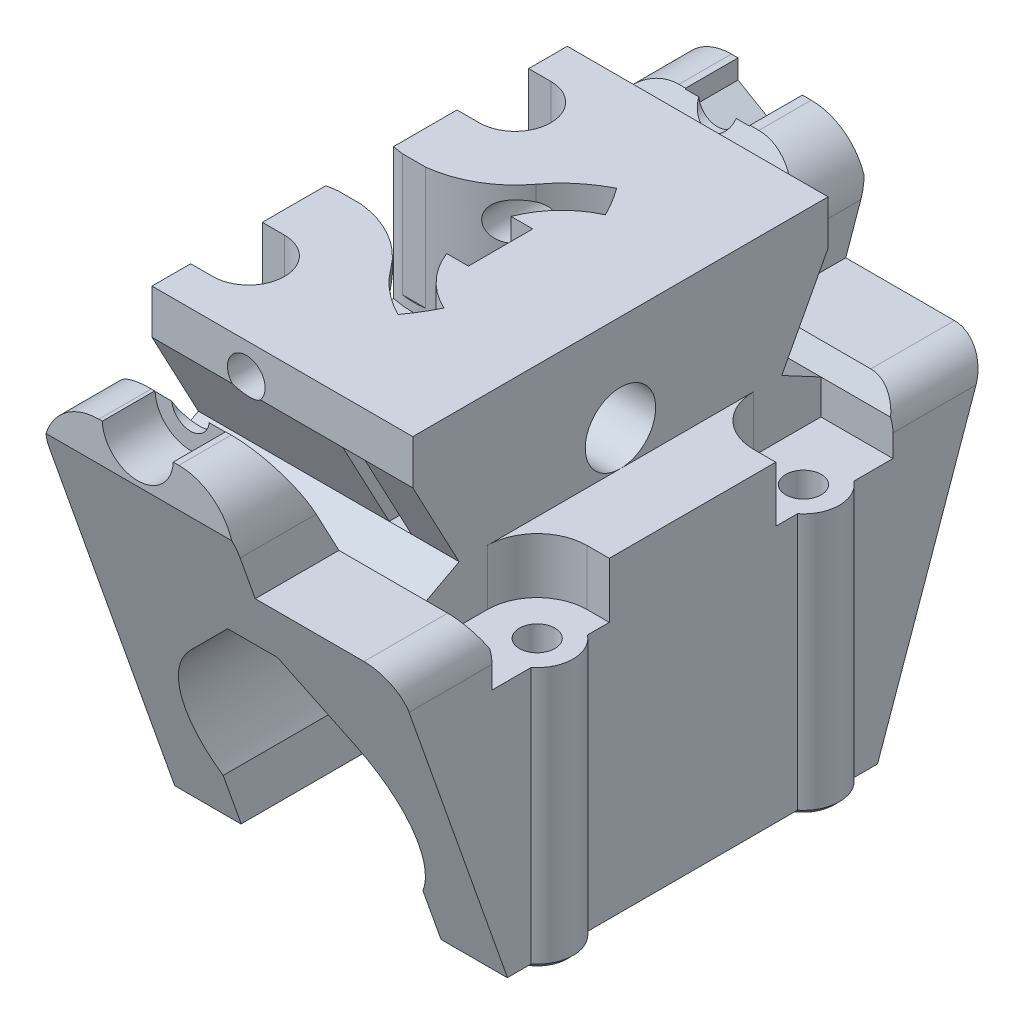
SolidWorks part; units mm, degrees
ref_plane "Front Plane" through (0, 0, 0) normal (0, 0, 1) x (1, 0, 0)
ref_plane "Top Plane" through (0, 0, 0) normal (0, 1, 0) x (1, 0, 0)
ref_plane "Right Plane" through (0, 0, 0) normal (1, 0, 0) x (0, 0, -1)
sketch "Sketch2" plane through (0, 0, 0) normal (1, 0, 0) x (0, 0, -1)
  line L0 (-104.5, 178.7) -> (-15, 10.5) construction
  line L1 (-15, -10.5) -> (15, -10.5) construction
  line L2 (-15, -10.5) -> (-15, 10.5) construction
  line L3 (-15, 10.5) -> (15, 10.5) construction
  line L4 (15, -10.5) -> (15, 10.5) construction
  line L5 (-15, -10.5) -> (15, 10.5) construction
  line L6 (-15, 10.5) -> (15, -10.5) construction
  line L7 (-18.7166, 26) -> (18.7166, 26) construction
  line L8 (0, 26) -> (0, -12.5) construction
  line L9 (-28.5, -10.5) -> (28.5, -10.5)
  line L10 (14.536, 18.1432) -> (18.7166, 26)
  line L11 (-16, 26) -> (28.5, -10.5) construction
  line L12 (-28.5, -10.5) -> (16, 26) construction
  line L13 (-29.5081, -14.5) -> (29.5081, -14.5) construction
  line L14 (-29.5081, -14.5) -> (-29.5081, -10.5) construction
  line L15 (-29.5081, -10.5) -> (29.5081, -10.5) construction
  line L16 (29.5081, -14.5) -> (29.5081, -10.5) construction
  line L17 (-29.5081, -14.5) -> (29.5081, -10.5) construction
  line L18 (-29.5081, -10.5) -> (29.5081, -14.5) construction
  line L19 (-104.5, 178.7) -> (104.5, 178.7) construction
  line L20 (-104.5, 178.7) -> (-104.5, -30.3) construction
  line L21 (-104.5, -30.3) -> (104.5, -30.3) construction
  line L22 (104.5, 178.7) -> (104.5, -30.3) construction
  line L23 (-104.5, 178.7) -> (104.5, -30.3) construction
  line L24 (-104.5, -30.3) -> (104.5, 178.7) construction
  line L25 (-14.536, 18.1432) -> (-18.0672, 16.2643)
  line L26 (-14.536, 18.1432) -> (-18.7166, 26)
  line L27 (-18.0672, 16.2643) -> (-23.7797, 27)
  line L28 (-28.5, 27) -> (-28.5, -10.5)
  line L29 (14.536, 18.1432) -> (18.0672, 16.2643)
  line L30 (-18.7166, 26) -> (-22.2478, 24.121) construction
  line L31 (28.5, 27) -> (28.5, -10.5)
  line L32 (18.7166, 26) -> (18.7166, 30)
  line L33 (18.7166, 30) -> (-18.7166, 30)
  line L34 (-18.7166, 30) -> (-18.7166, 26)
  line L35 (18.0672, 16.2643) -> (23.7797, 27)
  line L36 (22.2478, 24.121) -> (28.5, 24.121) construction
  line L37 (18.7166, 26) -> (22.2478, 24.121) construction
  line L38 (-22.2478, 24.121) -> (-28.5, 24.121) construction
  line L39 (23.7797, 27) -> (28.5, 27)
  line L40 (-23.7797, 27) -> (-28.5, 27)
  point P0 (0, 0)
  point P6 (0, 12.8764)
  point P11 (0, -12.5)
  point P16 (0, 74.2)
  point P32 (0, -10.5)
  dimension "D1" = 21
  dimension "D2" = 30
  dimension "D3" = 32
  dimension "D4" = 26
  dimension "D5" = 4
  dimension "D6" = 17.8
  dimension "D7" = 209
  dimension "D8" = 184
  dimension "D9" = 57
  dimension "D10" = 4
  dimension "D11" = 4
  dimension "D12" = 3
extrude "Boss-Extrude1" add sketch "Sketch2" along normal blind 30
chamfer "Chamfer4" distance 34 distance2 12 1 edges at (15, -10.5, 28.5) first distance on face at (15, 8.25, 28.5)
chamfer "Chamfer3" distance 12 distance2 34 1 edges at (15, -10.5, -28.5) first distance on face at (15, -10.5, -6)
sketch "Sketch3" plane through (0, 0, -28.5) normal (0, 0, -1) x (-1, 0, 0)
  line L0 (-30, -10.5) -> (0, -10.5) construction
  line L1 (-24, -5.4083) -> (-24, -10.5)
  line L2 (-24, -10.5) -> (-6, -10.5)
  line L3 (-6, -10.5) -> (-6, -5.4083)
  line L4 (-15, 0) -> (-7.5754, 7.4246) construction
  line L5 (-7.5754, 7.4246) -> (-12.7508, 12.6)
  line L6 (-12.7508, 12.6) -> (-17.2492, 12.6)
  line L7 (-17.2492, 12.6) -> (-22.4246, 7.4246)
  line L8 (-22.4246, 7.4246) -> (-15, 0) construction
  arc A0 (-6, -5.4083) -> (-7.5754, 7.4246) centre (-15, 0) ccw
  arc A1 (-22.4246, 7.4246) -> (-24, -5.4083) centre (-15, 0) ccw
  point P2 (-15, -10.5)
  point P12 (-15, 10.5)
  dimension "D1" = 21
  dimension "D2" = 18
  dimension "D3" = 2.1
extrude "Cut-Extrude1" cut sketch "Sketch3" against normal through all
sketch "Sketch4" plane through (0, -10.5, 0) normal (0, -1, 0) x (1, 0, 0)
  line L0 (0, 0) -> (30, 0) construction
  line L1 (30, 16.5) -> (30, -16.5) construction
  line L3 (2, -12) -> (28, -12) construction
  line L4 (2, -12) -> (2, 12) construction
  line L5 (2, 12) -> (28, 12) construction
  line L6 (28, -12) -> (28, 12) construction
  line L7 (2, -12) -> (28, 12) construction
  line L8 (2, 12) -> (28, -12) construction
  circle A0 centre (28, 12) radius 1.6
  circle A1 centre (28, -12) radius 1.6
  circle A2 centre (2, -12) radius 1.6
  circle A3 centre (2, 12) radius 1.6
  point P5 (15, 0)
  dimension "D3" = 3.2
  dimension "D1" = 26
  dimension "D2" = 24
extrude "Cut-Extrude2" cut sketch "Sketch4" against normal through all
chamfer "Chamfer1" [suppressed] distance 11 distance2 8
sketch "Sketch5" plane through (0, -10.5, 0) normal (0, -1, 0) x (1, 0, 0)
  line L0 (30, 14.536) -> (30, 9.464)
  line L1 (30, 16.5) -> (30, -16.5) construction
  line L2 (0, 14.536) -> (0, 9.464)
  line L3 (0, -9.464) -> (0, -14.536)
  line L4 (30, -9.464) -> (30, -14.536)
  line L5 (0, 16.5) -> (0, -16.5) construction
  arc A0 (30, 9.464) -> (30, 14.536) centre (28, 12) ccw
  arc A1 (30, -14.536) -> (30, -9.464) centre (28, -12) ccw
  arc A2 (0, -9.464) -> (0, -14.536) centre (2, -12) ccw
  arc A3 (0, 14.536) -> (0, 9.464) centre (2, 12) ccw
  circle A5 centre (28, -12) radius 1.6 construction
extrude "Boss-Extrude2" add sketch "Sketch5" along direction (0, 1, 0) on the side against the normal through all
sketch "Sketch7" plane through (0, 30, 0) normal (0, 1, 0) x (1, 0, 0)
  line L0 (2, 8.7703) -> (-1.2297, 8.7703)
  line L1 (15, 19.7808) -> (15, -19.7808) construction
  line L4 (-1.2297, 8.7703) -> (-1.2297, 15.2297)
  line L5 (0, 0) -> (30, 0) construction
  line L6 (31.2297, 15.2297) -> (28, 15.2297)
  line L7 (-1.2297, 15.2297) -> (2, 15.2297)
  line L8 (31.2297, 8.7703) -> (31.2297, 15.2297)
  line L9 (28, 8.7703) -> (31.2297, 8.7703)
  line L10 (28, -8.7703) -> (31.2297, -8.7703)
  line L11 (31.2297, -8.7703) -> (31.2297, -15.2297)
  line L12 (-1.2297, -15.2297) -> (2, -15.2297)
  line L13 (31.2297, -15.2297) -> (28, -15.2297)
  line L14 (-1.2297, -8.7703) -> (-1.2297, -15.2297)
  line L15 (2, -8.7703) -> (-1.2297, -8.7703)
  arc A0 (2, 8.7703) -> (2, 15.2297) centre (2, 12) ccw
  arc A1 (28, 8.7703) -> (28, 15.2297) centre (28, 12) cw
  arc A2 (28, -8.7703) -> (28, -15.2297) centre (28, -12) ccw
  arc A3 (2, -8.7703) -> (2, -15.2297) centre (2, -12) cw
  arc A4 (0, 14.536) -> (0, 9.464) centre (2, 12) ccw construction
extrude "Cut-Extrude6" cut sketch "Sketch7" against normal offset from surface (7 mm away) 33.5 up to face at (2, -10.5, 10.4)
ref_axis "Axis1" through (15, 0, 22.8263) along (0, 0, -1)
sketch "Sketch8" plane through (0, 30, 0) normal (0, 1, 0) x (1, 0, 0)
  line L1 (19.2, -29.9577) -> (17.2, -29.9577)
  line L2 (19.2, -18.7166) -> (19.2, -10.8167)
  line L3 (19.2, 29.9577) -> (17.2, 29.9577)
  line L4 (17.2, -29.9577) -> (17.2, -13.4164)
  line L5 (19.2, -29.9577) -> (17.2, 29.9577) construction
  line L6 (19.2, 29.9577) -> (17.2, -29.9577) construction
  line L7 (15, -22.8263) -> (15, 22.8263) construction
  line L8 (17.2, 13.4164) -> (17.2, 29.9577)
  line L9 (34.5, -29.9577) -> (23.5, -29.9577)
  line L10 (34.5, -29.9577) -> (34.5, 29.9577)
  line L11 (34.5, 29.9577) -> (23.5, 29.9577)
  line L12 (23.5034, -18.7166) -> (23.5034, 18.7166)
  line L13 (34.5, -29.9577) -> (23.5, 29.9577) construction
  line L14 (34.5, 29.9577) -> (23.5, -29.9577) construction
  line L15 (19.2, 10.8167) -> (19.2, 19.7808)
  line L16 (-7.1604, 12) -> (-7.1604, 28.5)
  line L17 (-7.1604, 28.5) -> (-15.4886, 28.5)
  line L18 (-15.4886, 28.5) -> (-15.4886, -28.5)
  line L19 (-15.4886, 0) -> (29, 0) construction
  line L20 (-7.1604, -28.5) -> (-15.4886, -28.5)
  line L21 (-7.1604, -12) -> (-7.1604, -28.5)
  line L24 (19.2, 19.7808) -> (23.5034, 18.7166)
  line L25 (30, 18.7166) -> (0, 18.7166) construction
  line L26 (19.2, 29.9577) -> (23.5, 29.9577)
  line L27 (23.5034, -18.7166) -> (19.2, -18.7166)
  line L28 (30, -18.7166) -> (0, -18.7166) construction
  line L29 (19.2, -29.9577) -> (23.5, -29.9577)
  arc A0 (16.7455, 7.8667) -> (16.7455, -7.8667) centre (18.2, 0) ccw
  arc A1 (15.0571, 10.5415) -> (9.3609, 6.5475) centre (18.2, 0) ccw
  arc A2 (-7.1604, 12) -> (9.3609, 6.5475) centre (2, 12) ccw
  arc A3 (17.2, -13.4164) -> (15.0571, -10.5415) centre (14.2, -13.4164) ccw
  arc A4 (19.2, -10.8167) -> (16.7455, -7.8667) centre (16.2, -10.8167) ccw
  arc A5 (16.7455, 7.8667) -> (19.2, 10.8167) centre (16.2, 10.8167) ccw
  arc A6 (15.0571, 10.5415) -> (17.2, 13.4164) centre (14.2, 13.4164) ccw
  arc A8 (-7.1604, -12) -> (9.3609, -6.5475) centre (2, -12) cw
  arc A9 (9.3609, -6.5475) -> (15.0571, -10.5415) centre (18.2, 0) ccw
  point P0 (18.2, 0)
  point P10 (29, 0)
  point P32 (2, 12)
  point P40 (2, -12)
  dimension "D5" = 3
  dimension "D6" = 3
  dimension "D7" = 3
  dimension "D8" = 3
  dimension "D9" = 3
  dimension "D10" = 8
  dimension "D1" = 3.2
  dimension "D2" = 2
  dimension "D3" = 14
  dimension "D4" = 11
extrude "Cut-Extrude7" cut sketch "Sketch8" against normal up to vertex (11.8568 mm away) up to point (0, 18.1432, 14.536)
sketch "Sketch9" plane through (0, 18.1432, 0) normal (0, 1, 0) x (1, 0, 0)
  line L0 (5.2297, 12) -> (5.2297, 19.7808)
  line L2 (5.2297, 19.7808) -> (-1.2297, 19.7808)
  line L3 (-1.2297, 19.7808) -> (-1.2297, 8.7703)
  line L4 (-1.2297, 8.7703) -> (2, 8.7703)
  line L5 (0, 0) -> (30, 0) construction
  line L7 (15, 28.5567) -> (15, -28.5201) construction
  line L8 (15, -22.8263) -> (15, 22.8263) construction
  line L9 (31.2297, 8.7703) -> (28, 8.7703)
  line L10 (31.2297, 19.7808) -> (31.2297, 8.7703)
  line L11 (24.7703, 19.7808) -> (31.2297, 19.7808)
  line L12 (24.7703, 12) -> (24.7703, 19.7808)
  line L13 (24.7703, -12) -> (24.7703, -19.7808)
  line L14 (24.7703, -19.7808) -> (31.2297, -19.7808)
  line L15 (31.2297, -19.7808) -> (31.2297, -8.7703)
  line L16 (31.2297, -8.7703) -> (28, -8.7703)
  line L17 (-1.2297, -8.7703) -> (2, -8.7703)
  line L18 (-1.2297, -19.7808) -> (-1.2297, -8.7703)
  line L19 (5.2297, -19.7808) -> (-1.2297, -19.7808)
  line L20 (5.2297, -12) -> (5.2297, -19.7808)
  arc A0 (2, 8.7703) -> (5.2297, 12) centre (2, 12) ccw
  arc A1 (28, 8.7703) -> (24.7703, 12) centre (28, 12) cw
  arc A2 (28, -8.7703) -> (24.7703, -12) centre (28, -12) ccw
  arc A3 (2, -8.7703) -> (5.2297, -12) centre (2, -12) cw
extrude "Cut-Extrude8" [suppressed] cut sketch "Sketch9" against normal up to surface and the other way through all
sketch "Sketch10" plane through (0, 30, 0) normal (0, 1, 0) x (1, 0, 0)
  line L0 (5.1822, 15.7238) -> (5.1822, 18.7166)
  line L1 (5.1822, 18.7166) -> (23.5034, 18.7166)
  line L2 (23.5034, 18.7166) -> (23.5034, -18.7166)
  line L3 (23.5034, -18.7166) -> (5.1822, -18.7166)
  line L4 (5.1822, -18.7166) -> (5.1822, -15.7238)
  line L5 (23.5034, -18.7166) -> (23.5034, 18.7166) construction
  arc A0 (5.1822, -15.7238) -> (5.1822, 15.7238) centre (0, 0) ccw
extrude "Boss-Extrude3" add sketch "Sketch10" against normal blind 4
sketch "Sketch11" plane through (0, 18.1432, 0) normal (0, 1, 0) x (1, 0, 0)
  line L0 (23.5034, 12) -> (23.5034, 18.0672)
  line L1 (23.5034, -18.7166) -> (23.5034, 18.7166) construction
  line L2 (30, 18.0672) -> (0, 18.0672) construction
  line L3 (23.5034, 18.0672) -> (32.4966, 18.0672)
  line L4 (32.4966, 18.0672) -> (32.4966, 7.5034)
  line L5 (32.4966, 7.5034) -> (28, 7.5034)
  arc A0 (23.5034, 12) -> (28, 7.5034) centre (28, 12) ccw
extrude "Cut-Extrude9" cut sketch "Sketch11" against normal blind 5
mirror "Mirror1" about plane through (0, 0, 0) normal (0, 0, 1) of "Cut-Extrude9"
sketch "Sketch12" plane through (0, 0, 0) normal (0, 0, 1) x (1, 0, 0)
  line L0 (0, 27) -> (0, 23.5) construction
  line L1 (17.2, 18.1432) -> (0, 18.1432) construction
  circle A0 centre (8.5, 27.1432) radius 1.7
  dimension "D3" = 3.4
  dimension "D1" = 8.5
  dimension "D2" = 9
extrude "Cut-Extrude10" cut sketch "Sketch12" against normal through all and the other way through all
sketch "Sketch13" plane through (30, 0, 0) normal (1, 0, 0) x (0, 0, -1)
  line L0 (-19.067, 18.1432) -> (-22.2478, 24.121)
  line L1 (-28.5, 18.1432) -> (-19.067, 18.1432)
  line L2 (-28.5, 18.1432) -> (-28.5, 24.121)
  line L3 (-28.5, 24.121) -> (-22.2478, 24.121)
  line L4 (28.5, 18.1432) -> (28.5, 24.121)
  line L5 (-23.7797, 27) -> (-19.067, 18.1432) construction
  line L6 (19.067, 18.1432) -> (22.2478, 24.121)
  line L7 (19.067, 18.1432) -> (23.7797, 27) construction
  line L8 (19.067, 18.1432) -> (28.5, 18.1432)
  line L9 (22.2478, 24.121) -> (28.5, 24.121)
extrude "Cut-Extrude11" cut sketch "Sketch13" against normal up to surface (12.8 mm away) up to face at (17.2, 22.7573, 25.2912)
sketch "Sketch14" plane through (23.5034, 0, 0) normal (1, 0, 0) x (0, 0, -1)
  line L0 (7.5034, 18.1432) -> (-7.5034, 18.1432) construction
  circle A0 centre (0, 21.3182) radius 1.7
  point P2 (0, 18.1432)
  dimension "D1" = 3.4
  dimension "D2" = 3.175
extrude "Cut-Extrude12" cut sketch "Sketch14" against normal through all
sketch "Sketch15" plane through (23.5034, 0, 0) normal (1, 0, 0) x (0, 0, -1)
  circle A0 centre (0, 21.3182) radius 3.175
extrude "Cut-Extrude13" cut sketch "Sketch15" against normal blind 6
ref_plane "Plane1" through (10.2, 0, 0) normal (-1, 0, 0) x (0, 0, 1)
sketch "Sketch16" plane through (10.2, 0, 0) normal (-1, 0, 0) x (0, 0, 1)
  line L0 (-2.9, 30) -> (2.9, 30)
  line L1 (0, 17.3152) -> (2.9, 18.9895)
  line L2 (2.9, 18.9895) -> (2.9, 30)
  line L3 (2.9, 22.3381) -> (0, 24.0124) construction
  line L4 (0, 24.0124) -> (-2.9, 22.3381) construction
  line L5 (-2.9, 30) -> (-2.9, 18.9895)
  line L6 (-2.9, 18.9895) -> (0, 17.3152)
  line L7 (7.2748, 30) -> (-7.2748, 30) construction
  circle A0 centre (0, 20.6638) radius 2.9 construction
  point P12 (0, 21.3182)
  dimension "D1" = 5.8
extrude "Cut-Extrude14" cut sketch "Sketch16" against normal blind 2.5 and the other way through all
sketch "Sketch17" plane through (0, 0, 28.5) normal (0, 0, 1) x (1, 0, 0)
  line L0 (5.3, 27.1432) -> (5.3, 31.7822)
  line L1 (5.3, 31.7822) -> (11.7, 31.7822)
  line L2 (11.7, 31.7822) -> (11.7, 27.1432)
  arc A0 (5.3, 27.1432) -> (11.7, 27.1432) centre (8.5, 27.1432) ccw
  dimension "D1" = 6.4
extrude "Cut-Extrude15" cut sketch "Sketch17" against normal offset from surface (4.75 mm away) 23.75 up to plane "Front Plane"
sketch "Sketch18" plane through (0, 0, -28.5) normal (0, 0, -1) x (-1, 0, 0)
  line L0 (-11.4, 31.9524) -> (-5.6, 31.9524)
  line L1 (-8.5, 23.5946) -> (-5.6, 25.2689)
  line L2 (-5.6, 25.2689) -> (-5.6, 31.9524)
  line L3 (-5.6, 28.6176) -> (-8.5, 30.2919) construction
  line L4 (-8.5, 30.2919) -> (-11.4, 28.6176) construction
  line L5 (-11.4, 31.9524) -> (-11.4, 25.2689)
  line L6 (-11.4, 25.2689) -> (-8.5, 23.5946)
  circle A0 centre (-8.5, 26.9432) radius 2.9 construction
  point P1 (-8.5, 27.1432)
  dimension "D1" = 5.8
  dimension "D2" = 0.2
extrude "Cut-Extrude16" cut sketch "Sketch18" against normal offset from surface (4.75 mm away) 23.75 up to plane "Front Plane"
fillet "Fillet1" radius 5 4 edges at (0, 27, -26.1399) (17.2, 27, -26.1399) (17.2, 27, 26.1399) (0, 27, 26.1399)
fillet "Fillet2" radius 3 2 edges at (30, 18.1432, -22.8382) (30, 18.1432, 22.8382)
chamfer "Chamfer2" distance 0.5 angle 45 20 edges at (30, -10.5, 15.518) (31.2297, -10.5, 12) (30, -10.5, 0) (31.2297, -10.5, -12) (30, -10.5, -15.518) (24, -10.5, 0) (28, -10.5, 10.4) (28, -10.5, -13.6) (0, -10.5, -15.518) (-1.2297, -10.5, -12) (0, -10.5, 0) (-1.2297, -10.5, 12) (0, -10.5, 15.518) (6, -10.5, 0) (2, -10.5, -13.6) (2, -10.5, 10.4) (27, -10.5, 16.5) (3, -10.5, 16.5) (27, -10.5, -16.5) (3, -10.5, -16.5) first distance on face at (30, 5.9288, 17.8761) first distance on face at (30.6149, 1.3216, 12) first distance on face at (30, 8.4824, 0) first distance on face at (30.6149, 1.3216, -12) first distance on face at (30, 5.9288, -17.8761) first distance on face at (24, -7.9542, 0) first distance on face at (28, -10.5, -13.6) first distance on face at (0, 9.5679, -18.7882) first distance on face at (-0.4919, 8.6286, -12.5072) first distance on face at (0, 18.7259, 0) first distance on face at (-0.4919, 8.6286, 12.5072) first distance on face at (0, 9.5679, 18.7882) first distance on face at (6, -7.9542, 0) first distance on face at (2, -10.5, 10.4) first distance on face at (15.2483, 7.6967, 22.9224) first distance on face at (15.2483, 7.6967, -22.9224)
equation "\"D1@Sketch8\" = 9 - ( 11.6 / 2 )"
equation "\"D2@Sketch14\"=6.35/2"
